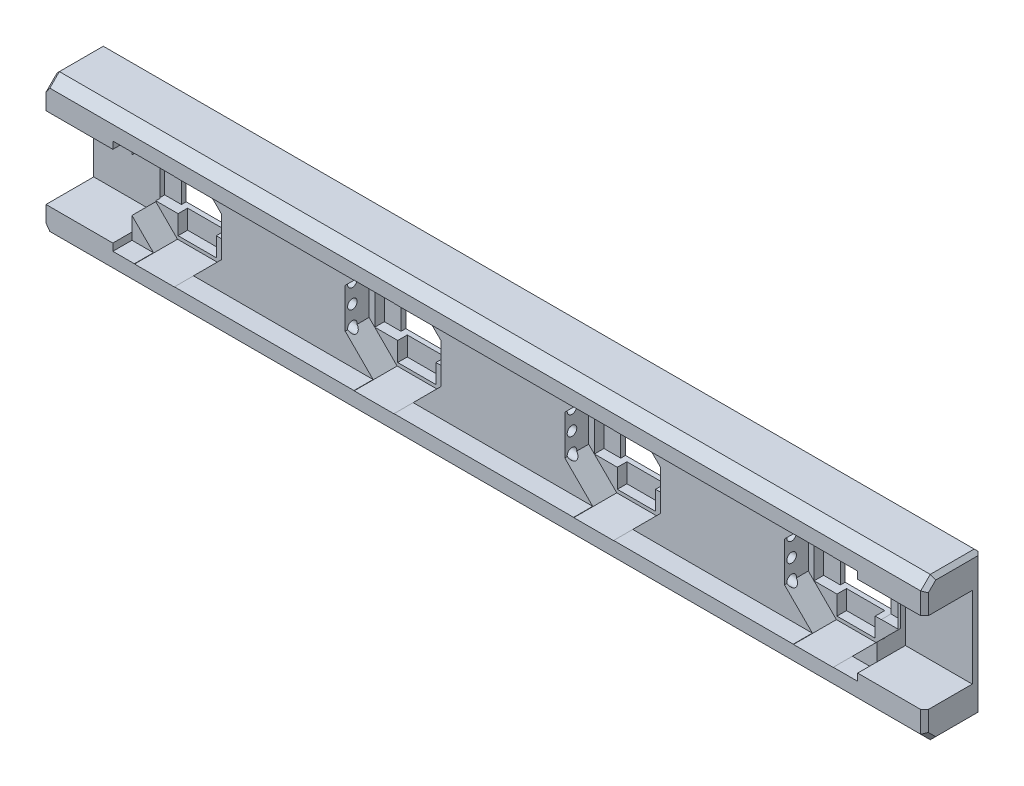
SolidWorks part; units mm, degrees
ref_plane "Front Plane" through (0, 0, 0) normal (0, 0, 1) x (1, 0, 0)
ref_plane "Top Plane" through (0, 0, 0) normal (0, 1, 0) x (1, 0, 0)
ref_plane "Right Plane" through (0, 0, 0) normal (1, 0, 0) x (0, 0, -1)
sketch "Sketch1" plane through (0, 0, 0) normal (0, 0, 1) x (1, 0, 0)
  line L1 (-45.75, 25.6543) -> (46.25, 25.6543)
  line L2 (-45.75, 25.6543) -> (-45.75, 10.6543)
  line L3 (-45.75, 10.6543) -> (46.25, 10.6543)
  line L4 (46.25, 25.6543) -> (46.25, 10.6543)
  dimension "D1" = 92
  dimension "D2" = 15
extrude "Boss-Extrude1" add sketch "Sketch1" along normal blind 6
sketch "Sketch12" plane through (46.25, 0, 0) normal (1, 0, 0) x (0, 0, -1)
  line L0 (-6, 25.6543) -> (-6, 24.6543)
  line L1 (-6, 10.6543) -> (-6, 25.6543) construction
  line L2 (-6, 24.6543) -> (-5, 25.6543)
  line L3 (-6, 25.6543) -> (0, 25.6543) construction
  line L4 (-5, 25.6543) -> (-6, 25.6543)
  line L5 (-6, 10.6543) -> (-5, 10.6543)
  line L6 (-6, 10.6543) -> (0, 10.6543) construction
  line L7 (-5, 10.6543) -> (-6, 11.6543)
  line L8 (-6, 10.6543) -> (-6, 25.6543) construction
  line L9 (-6, 11.6543) -> (-6, 10.6543)
  dimension "D1" = 1
  dimension "D2" = 1
  dimension "D3" = 1
extrude "Cut-Extrude8" cut sketch "Sketch12" against normal blind 92
sketch "Sketch13" plane through (0, 0, 0) normal (0, 0, -1) x (-1, 0, 0)
  line L0 (45.75, 25.6543) -> (45.75, 10.6543) construction
  line L1 (43.25, 23.1543) -> (43.75, 23.1543)
  line L2 (43.25, 23.1543) -> (43.25, 13.1543)
  line L3 (43.25, 13.1543) -> (43.75, 13.1543)
  line L4 (43.75, 23.1543) -> (43.75, 13.1543)
  line L5 (-46.25, 25.6543) -> (45.75, 25.6543) construction
  dimension "D1" = 2
  dimension "D2" = 0.5
  dimension "D3" = 10
  dimension "D4" = 2.5
extrude "Cut-Extrude9" cut sketch "Sketch13" against normal blind 0.6
fillet "Fillet1" radius 0.25 1 edges at (-43.75, 18.1543, 0)
fillet "Fillet2" radius 0.25 4 edges at (-43.5, 23.1543, 0.6) (-43.75, 18.1543, 0.6) (-43.5, 13.1543, 0.6) (-43.25, 18.1543, 0.6)
chamfer "Chamfer1" distance 0.4 angle 45 2 edges at (0.25, 10.6543, 0) (0.25, 25.6543, 0)
chamfer "Chamfer2" distance 0.4 angle 45 2 edges at (46.25, 18.1543, 0) (-45.75, 18.1543, 0)
chamfer "Chamfer3" distance 0.4 angle 45 2 edges at (-45.75, 10.6543, 2.7) (-45.75, 25.6543, 2.7)
chamfer "Chamfer4" distance 0.4 angle 45 2 edges at (-45.75, 11.3543, 5.7) (-45.75, 24.9543, 5.7)
chamfer "Chamfer5" distance 0.4 angle 45 5 edges at (46.25, 25.1543, 5.5) (46.25, 25.6543, 2.7) (46.25, 18.1543, 6) (46.25, 11.1543, 5.5) (46.25, 10.6543, 2.7)
sketch "Sketch15" plane through (0, 0, 6) normal (0, 0, 1) x (1, 0, 0)
  line L0 (-45.75, 24.0886) -> (-45.75, 12.22) construction
  line L1 (-29.3821, 20.2328) -> (-32.3215, 23.1722)
  line L2 (-32.3215, 23.1722) -> (-36.4785, 23.1722)
  line L3 (-36.4785, 23.1722) -> (-39.4179, 20.2328)
  line L4 (-39.4179, 20.2328) -> (-39.4179, 16.0758)
  line L5 (-39.4179, 16.0758) -> (-36.4785, 13.1364)
  line L6 (-36.4785, 13.1364) -> (-32.3215, 13.1364)
  line L7 (-32.3215, 13.1364) -> (-29.3821, 16.0758)
  line L8 (-29.3821, 16.0758) -> (-29.3821, 20.2328)
  line L9 (-45.35, 25.6543) -> (45.85, 25.6543) construction
  line L10 (-45.35, 11.6543) -> (45.85, 11.6543) construction
  circle A0 centre (-34.4, 18.1543) radius 5.0179 construction
  point P14 (0, 0)
  dimension "D1" = 11.35
  dimension "D2" = 7.5
extrude "Cut-Extrude10" cut sketch "Sketch15" against normal blind 4.5
sketch "Sketch16" plane through (0, 0, 1.5) normal (0, 0, 1) x (1, 0, 0)
  line L1 (-37.0679, 20.7864) -> (-31.7679, 20.7864)
  line L2 (-37.0679, 20.7864) -> (-37.0679, 15.4864)
  line L3 (-37.0679, 15.4864) -> (-31.7679, 15.4864)
  line L4 (-31.7679, 20.7864) -> (-31.7679, 15.4864)
  line L5 (-39.4179, 20.2328) -> (-39.4179, 16.0758) construction
  line L6 (-36.4785, 13.1364) -> (-32.3215, 13.1364) construction
  point P4 (-37.0679, 18.1364)
  point P7 (-39.4179, 18.1543)
  point P10 (-34.4, 13.1364)
  point P11 (-34.4179, 15.4864)
  dimension "D1" = 5.3
  dimension "D2" = 5.3
  dimension "D3" = 2.35
  dimension "D4" = 2.35
extrude "Cut-Extrude11" cut sketch "Sketch16" against normal blind 4.5
sketch "Sketch17" plane through (0, 0, 1.5) normal (0, 0, 1) x (1, 0, 0)
  line L0 (-37.0679, 15.4864) -> (-31.7679, 15.4864) construction
  line L1 (-36.4179, 15.4864) -> (-32.4179, 15.4864)
  line L2 (-36.4179, 15.4864) -> (-36.4179, 13.4864)
  line L3 (-36.4179, 13.4864) -> (-32.4179, 13.4864)
  line L4 (-32.4179, 15.4864) -> (-32.4179, 13.4864)
  line L5 (-31.7679, 20.7864) -> (-37.0679, 20.7864) construction
  line L6 (-36.4179, 20.7864) -> (-32.4179, 20.7864)
  line L7 (-36.4179, 20.7864) -> (-36.4179, 22.7864)
  line L8 (-36.4179, 22.7864) -> (-32.4179, 22.7864)
  line L9 (-32.4179, 20.7864) -> (-32.4179, 22.7864)
  line L10 (-31.7679, 15.4864) -> (-31.7679, 20.7864) construction
  dimension "D1" = 4
  dimension "D2" = 4
  dimension "D3" = 2
  dimension "D4" = 2
  dimension "D5" = 0.65
  dimension "D6" = 0.65
extrude "Cut-Extrude12" cut sketch "Sketch17" against normal blind 1
sketch "Sketch18" plane through (0, 0, 1.5) normal (0, 0, 1) x (1, 0, 0)
  line L1 (-37.0679, 15.4864) -> (-38.8179, 15.4864)
  line L2 (-37.0679, 15.4864) -> (-37.0679, 20.8045)
  line L3 (-37.0679, 20.8045) -> (-38.8179, 20.8045)
  line L4 (-38.8179, 15.4864) -> (-38.8179, 20.8045)
  line L5 (-31.7679, 20.7864) -> (-30.0179, 20.7864)
  line L6 (-31.7679, 20.7864) -> (-31.7679, 15.5045)
  line L7 (-31.7679, 15.5045) -> (-30.0179, 15.5045)
  line L8 (-30.0179, 20.7864) -> (-30.0179, 15.5045)
  dimension "D1" = 1.75
  dimension "D2" = 1.75
extrude "Cut-Extrude13" cut sketch "Sketch18" against normal blind 1
pattern_linear "LPattern1" count 4 spacing 23 along (1, 0, 0) of "Cut-Extrude10", "Cut-Extrude11", "Cut-Extrude12", "Cut-Extrude13"
sketch "Sketch19" plane through (0, 0, 6) normal (0, 0, 1) x (1, 0, 0)
  line L0 (-45.75, 24.0886) -> (-45.75, 12.22) construction
  line L1 (-45.75, 22.4043) -> (-38.75, 22.4043)
  line L2 (-45.75, 22.4043) -> (-45.75, 13.9043)
  line L3 (-45.75, 13.9043) -> (-38.75, 13.9043)
  line L4 (-38.75, 22.4043) -> (-38.75, 13.9043)
  line L6 (-45.35, 10.6543) -> (45.85, 10.6543) construction
  line L14 (46.25, 24.4886) -> (46.25, 11.82) construction
  line L15 (46.25, 22.4043) -> (39.25, 22.4043)
  line L16 (46.25, 22.4043) -> (46.25, 13.9043)
  line L17 (46.25, 13.9043) -> (39.25, 13.9043)
  line L18 (39.25, 22.4043) -> (39.25, 13.9043)
  dimension "D1" = 8.5
  dimension "D2" = 3.25
  dimension "D3" = 7
  dimension "D4" = 8.5
  dimension "D5" = 7
  dimension "D6" = 3.25
extrude "Cut-Extrude14" cut sketch "Sketch19" against normal blind 5
sketch "Sketch20" plane through (0, 0, 6) normal (0, 0, 1) x (1, 0, 0)
  line L0 (-45.35, 10.6543) -> (45.85, 10.6543) construction
  line L1 (39.25, 13.1543) -> (-38.75, 13.1543)
  line L2 (39.25, 13.1543) -> (39.25, 23.1543)
  line L3 (39.25, 23.1543) -> (-38.75, 23.1543)
  line L4 (-38.75, 13.1543) -> (-38.75, 23.1543)
  line L6 (-38.75, 20.9007) -> (-38.75, 22.4043) construction
  dimension "D1" = 10
  dimension "D2" = 2.5
  dimension "D3" = 0
extrude "Cut-Extrude15" cut sketch "Sketch20" against normal blind 2
sketch "Sketch21" plane through (29.5821, 0, 0) normal (1, 0, 0) x (0, 0, -1)
  line L1 (-1.5, 20.2328) -> (-4, 20.2328) construction
  line L2 (-4, 16.0758) -> (-4, 20.2328) construction
  circle A0 centre (-3.25, 18.1628) radius 0.5
  circle A1 centre (-3.25, 20.1628) radius 0.5
  circle A2 centre (-3.25, 16.1628) radius 0.5
  dimension "D2" = 1
  dimension "D3" = 1
  dimension "D4" = 1
  dimension "D1" = 2.07
  dimension "D5" = 2
  dimension "D6" = 2
  dimension "D7" = 0.75
extrude "Cut-Extrude16" cut sketch "Sketch21" against normal through all both and the other way through all
